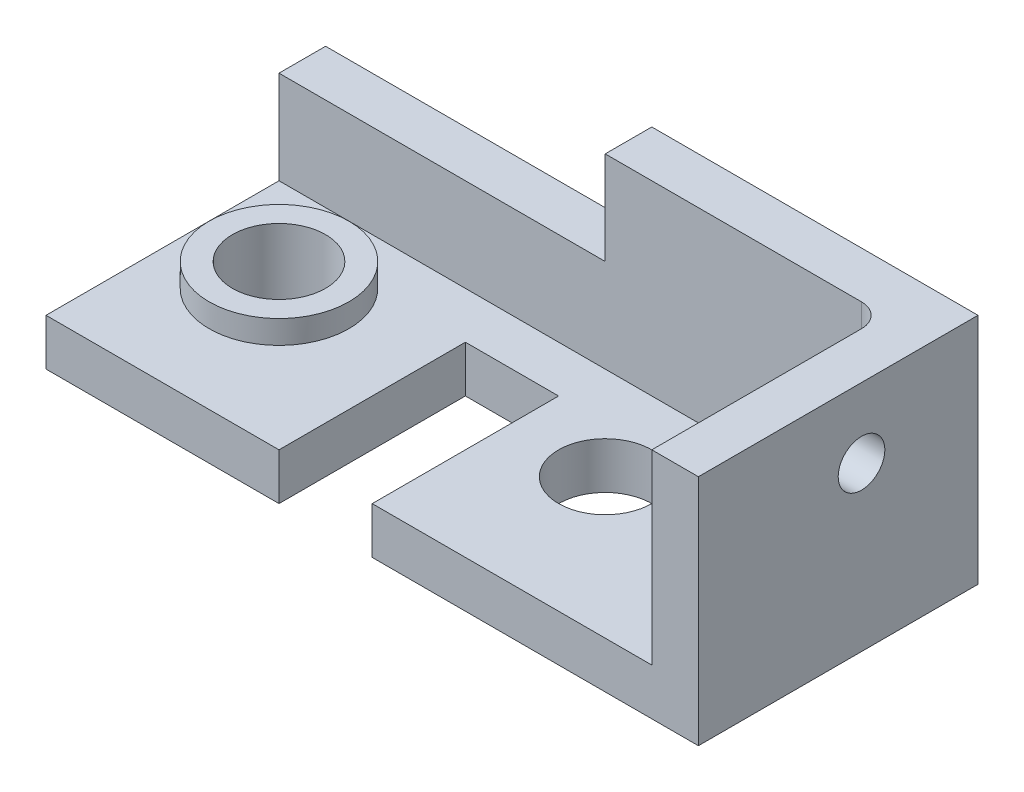
SolidWorks part; units mm, degrees
ref_plane "Ön Düzlem" through (0, 0, 0) normal (0, 0, 1) x (1, 0, 0)
ref_plane "Üst Düzlem" through (0, 0, 0) normal (0, 1, 0) x (1, 0, 0)
ref_plane "Sağ Düzlem" through (0, 0, 0) normal (1, 0, 0) x (0, 0, -1)
sketch "Çizim1" plane through (0, 0, 0) normal (0, 0, 1) x (1, 0, 0)
  line L1 (0, 0) -> (140, 0)
  line L2 (0, 0) -> (0, 50)
  line L3 (0, 50) -> (140, 50)
  line L4 (140, 0) -> (140, 50)
  dimension "D1" = 50
  dimension "D2" = 140
extrude "Yükseklik-Ekstrüzyon1" add sketch "Çizim1" along normal blind 60
sketch "Çizim2" plane through (0, 50, 0) normal (0, 1, 0) x (1, 0, 0)
  line L0 (140, 0) -> (0, 0) construction
  line L1 (0, -60) -> (130, -60)
  line L2 (0, -60) -> (0, -10)
  line L3 (0, -10) -> (130, -10)
  line L4 (130, -60) -> (130, -10)
  line L6 (140, -60) -> (140, 0) construction
  dimension "D1" = 10
  dimension "D2" = 10
extrude "Kes-Ekstrüzyon1" cut sketch "Çizim2" against normal blind 40
fillet "Radyus1" radius 5 1 edges at (130, 30, 10)
sketch "Çizim3" plane through (0, 10, 0) normal (0, 1, 0) x (1, 0, 0)
  line L0 (140, 0) -> (0, 0) construction
  line L1 (0, -10) -> (0, -60) construction
  circle A0 centre (20, -30) radius 15
  circle A1 centre (20, -30) radius 10
  dimension "D1" = 30
  dimension "D2" = 30
  dimension "D3" = 20
  dimension "D4" = 20
extrude "Yükseklik-Ekstrüzyon2" add sketch "Çizim3" along normal blind 5
extrude "Kes-Ekstrüzyon2" cut sketch "Çizim3<2>" against normal through all contours A1
sketch "Çizim3<2>" plane through (0, 10, 0) normal (0, 1, 0) x (1, 0, 0) same geometry as "Çizim3"
sketch "Çizim5" plane through (0, 0, 10) normal (0, 0, 1) x (1, 0, 0)
  line L1 (0, 50) -> (70, 50)
  line L2 (0, 50) -> (0, 30)
  line L3 (0, 30) -> (70, 30)
  line L4 (70, 50) -> (70, 30)
  dimension "D1" = 70
  dimension "D2" = 20
extrude "Kes-Ekstrüzyon3" cut sketch "Çizim5" against normal through all
sketch "Çizim6" plane through (0, 10, 0) normal (0, 1, 0) x (1, 0, 0)
  line L0 (0, -60) -> (130, -60) construction
  line L1 (70, -20) -> (50, -20)
  line L2 (70, -20) -> (70, -60)
  line L3 (70, -60) -> (50, -60)
  line L4 (50, -20) -> (50, -60)
  point P7 (0, 0)
  dimension "D1" = 20
  dimension "D2" = 40
extrude "Kes-Ekstrüzyon5" cut sketch "Çizim6" against normal through all
sketch "Çizim7" plane through (0, 10, 0) normal (0, 1, 0) x (1, 0, 0)
  line L0 (90, -30) -> (90, -20) construction
  line L1 (70, -60) -> (70, -20) construction
  circle A0 centre (90, -30) radius 10
  point P2 (0, 0)
  dimension "D1" = 20
  dimension "D2" = 20
extrude "Kes-Ekstrüzyon6" cut sketch "Çizim7" against normal through all
sketch "Çizim8" plane through (130, 0, 0) normal (-1, 0, 0) x (0, 0, 1)
  line L0 (0, 30) -> (0, 50) construction
  line L1 (60, 50) -> (15, 50) construction
  circle A0 centre (25, 35) radius 5
  dimension "D1" = 25
  dimension "D2" = 15
  dimension "D3" = 10
extrude "Kes-Ekstrüzyon7" cut sketch "Çizim8" against normal through all
